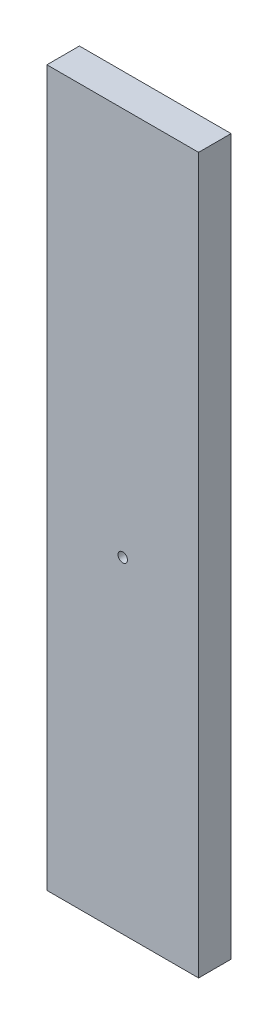
SolidWorks part; units mm, degrees
ref_plane "Front Plane" through (0, 0, 0) normal (0, 0, 1) x (1, 0, 0)
ref_plane "Top Plane" through (0, 0, 0) normal (0, 1, 0) x (1, 0, 0)
ref_plane "Right Plane" through (0, 0, 0) normal (1, 0, 0) x (0, 0, -1)
sketch "Sketch1" plane through (0, 0, 0) normal (0, 1, 0) x (1, 0, 0)
  line L1 (0, 0) -> (88.9, 0)
  line L2 (0, 0) -> (0, 19.05)
  line L3 (0, 19.05) -> (88.9, 19.05)
  line L4 (88.9, 0) -> (88.9, 19.05)
  dimension "D1" = 19.05
  dimension "D2" = 88.9
extrude "Boss-Extrude1" add sketch "Sketch1" along normal blind 419.1
sketch "Sketch2" plane through (0, 0, 0) normal (0, 0, 1) x (1, 0, 0)
  line L0 (44.45, 419.1) -> (44.45, 191.3014) construction
  line L1 (0, 419.1) -> (88.9, 419.1) construction
  line L2 (-349.25, 239.6416) -> (44.45, 191.3014) construction
  line L3 (-349.25, 239.6416) -> (-39.4224, 239.6416) construction
  circle A0 centre (44.45, 191.3014) radius 2.7781
  circle A1 centre (-349.25, 239.6416) radius 2.7781 construction
  circle A2 centre (-349.25, 239.6416) radius 2.7781 construction
  dimension "D1" = 5.5562
  dimension "D2" = 7
extrude "Cut-Extrude1" cut sketch "Sketch2" against normal through all
equation "\"DROPANGLE\" = 10"
